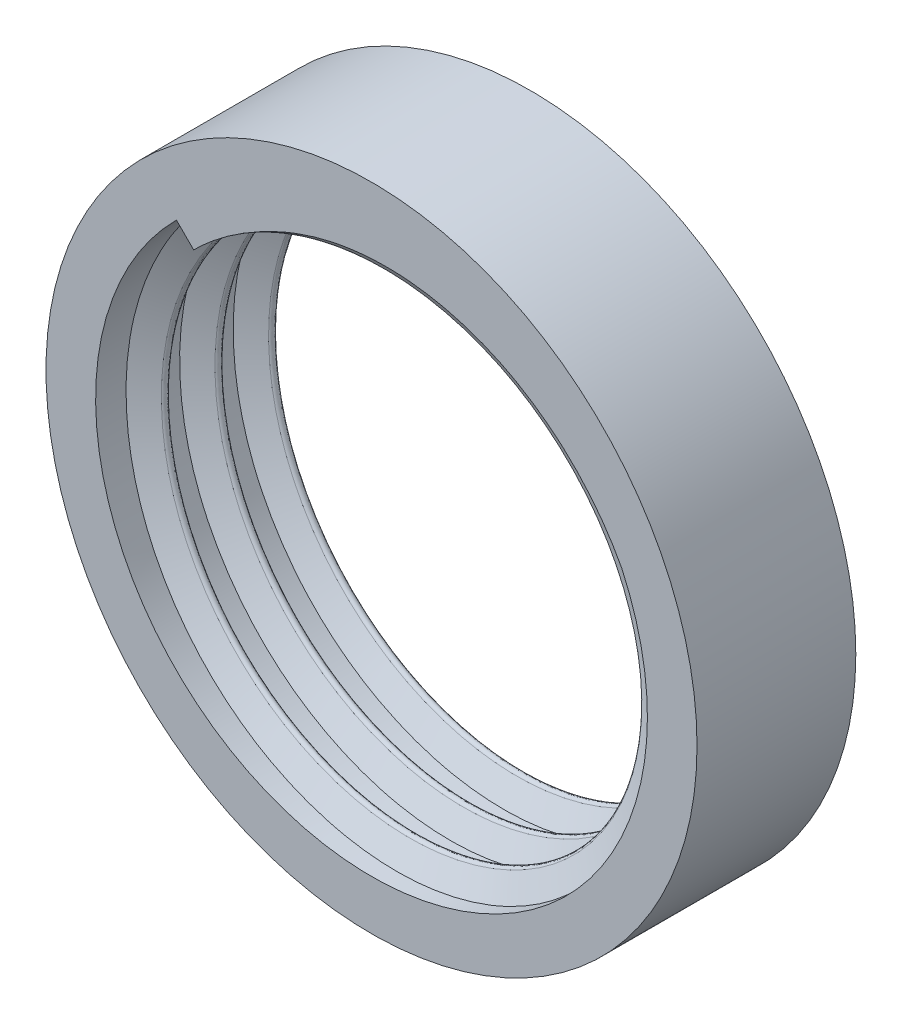
SolidWorks part; units mm, degrees
ref_plane "Ebene vorne" through (0, 0, 0) normal (0, 0, 1) x (1, 0, 0)
ref_plane "Ebene oben" through (0, 0, 0) normal (0, 1, 0) x (1, 0, 0)
ref_plane "Ebene rechts" through (0, 0, 0) normal (1, 0, 0) x (0, 0, -1)
sketch "Skizze1" plane through (0, 0, 0) normal (0, 0, 1) x (1, 0, 0)
  circle A0 centre (0, 0) radius 13.9
  circle A1 centre (0, 0) radius 16.4
  dimension "D1" = 27.8
  dimension "D2" = 2.5
extrude "Aufsatz-Linear austragen1" add sketch "Skizze1" along normal blind 8
sketch "Skizze2" plane through (0, 0, 8) normal (0, 0, 1) x (1, 0, 0)
  circle A0 centre (0, 0) radius 13.9
  circle A1 centre (0, 0) radius 13.9 construction
curve "Spirale/Helix1" pitch 2.7 height 16.2 radius 13.9 centre (0, 0, 8) axis (0, 0, -1) start towards (-0.7071, 0.7071, 0)
ref_plane "Ebene1" through (-9.8288, 9.8288, -8.2) normal (0.7068, 0.7068, -0.0309) x (-0.0218, -0.0218, -0.9995)
sketch "Skizze10" plane through (-9.8288, 9.8288, -8.2) normal (0.7068, 0.7068, -0.0309) x (-0.0218, -0.0218, -0.9995)
  line L0 (0, 0) -> (0, -1.4289) construction
  line L1 (0.1732, -1.1289) -> (0.825, 0)
  line L2 (0.825, 0) -> (-0.825, 0)
  line L3 (-0.1732, -1.1289) -> (-0.825, 0)
  arc A1 (0.1732, -1.1289) -> (-0.1732, -1.1289) centre (0, -1.0289) cw
  dimension "D2" = 60
  dimension "D4" = 0.2
  dimension "D1" = 1.65
  dimension "D3" = 60
sweep "Austragung1" add profiles "Skizze10" path "Spirale/Helix1"
sketch "Skizze12" plane through (0, 0, 8) normal (0, 0, 1) x (1, 0, 0)
  circle A0 centre (0, 0) radius 16.4 construction
  circle A1 centre (0, 0) radius 16.4
extrude "Schnitt-Linear austragen1" cut sketch "Skizze12" along normal through all
sketch "Skizze13" plane through (0, 0, 0) normal (0, 0, -1) x (-1, 0, 0)
  circle A0 centre (0, 0) radius 16.4 construction
  circle A1 centre (0, 0) radius 16.4
extrude "Schnitt-Linear austragen2" cut sketch "Skizze13" along normal through all
